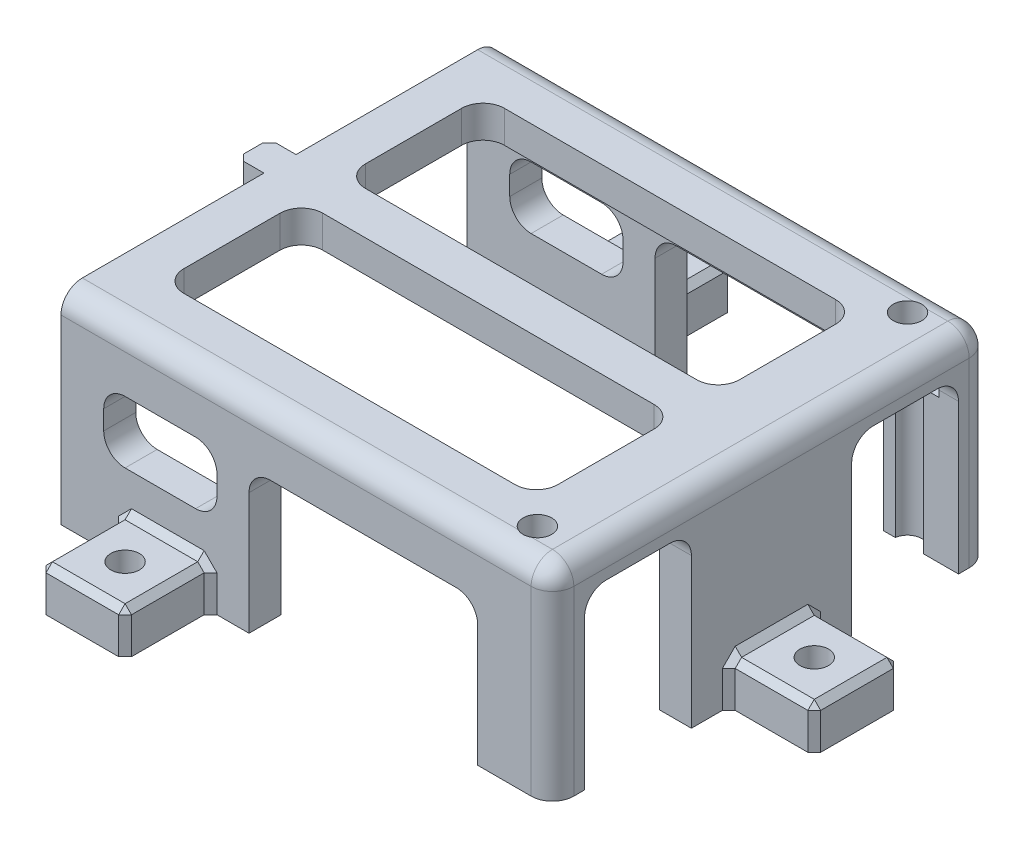
SolidWorks part; units mm, degrees
ref_plane "Front Plane" through (0, 0, 0) normal (0, 0, 1) x (1, 0, 0)
ref_plane "Top Plane" through (0, 0, 0) normal (0, 1, 0) x (1, 0, 0)
ref_plane "Right Plane" through (0, 0, 0) normal (1, 0, 0) x (0, 0, -1)
sketch "Sketch1" plane through (0, 0, 0) normal (0, 1, 0) x (1, 0, 0)
  line L0 (-27.305, 22.225) -> (-27.305, 26.035)
  line L1 (-27.305, -22.225) -> (27.305, -22.225)
  line L3 (-27.305, 22.225) -> (27.305, 22.225)
  line L4 (27.305, -22.225) -> (27.305, 22.225)
  line L5 (-27.305, -22.225) -> (27.305, 22.225) construction
  line L6 (-27.305, 22.225) -> (27.305, -22.225) construction
  line L7 (-27.305, -26.035) -> (31.115, -26.035)
  line L9 (-27.305, 26.035) -> (31.115, 26.035)
  line L10 (31.115, -26.035) -> (31.115, 26.035)
  line L11 (-27.305, -22.847) -> (31.115, 26.035) construction
  line L12 (-27.305, 22.847) -> (31.115, -26.035) construction
  line L13 (-27.305, -22.225) -> (-27.305, -26.035)
  point P0 (0, 0)
  point P6 (0, 0)
  dimension "D1" = 54.61
  dimension "D2" = 58.42
  dimension "D3" = 52.07
  dimension "D4" = 44.45
extrude "Boss-Extrude1" add sketch "Sketch1" along normal blind 20.32
sketch "Sketch2" plane through (0, 20.32, 0) normal (0, 1, 0) x (1, 0, 0)
  line L1 (-27.305, 26.035) -> (31.115, 26.035)
  line L2 (-27.305, 26.035) -> (-27.305, -26.035)
  line L3 (-27.305, -26.035) -> (31.115, -26.035)
  line L4 (31.115, 26.035) -> (31.115, -26.035)
extrude "Boss-Extrude2" add sketch "Sketch2" along normal blind 3.81
sketch "Sketch3" plane through (27.305, 0, 0) normal (-1, 0, 0) x (0, 0, 1)
  line L0 (-22.225, 0) -> (22.225, 0) construction
  line L1 (-22.225, 20.32) -> (-9.525, 20.32)
  line L2 (-22.225, 20.32) -> (-22.225, 0)
  line L3 (-22.225, 0) -> (-9.525, 0)
  line L4 (-9.525, 20.32) -> (-9.525, 0)
  line L6 (22.225, 20.32) -> (9.525, 20.32)
  line L7 (22.225, 20.32) -> (22.225, 0)
  line L8 (22.225, 0) -> (9.525, 0)
  line L9 (9.525, 20.32) -> (9.525, 0)
  dimension "D1" = 12.7
extrude "Cut-Extrude1" cut sketch "Sketch3" against normal up to surface (3.81 mm away) up to face at (31.115, 12.065, 0)
fillet "Fillet2" radius 2.54 3 edges at (31.115, 12.065, -26.035) (31.115, 12.065, 26.035) (31.115, 24.13, 0)
sketch "Sketch4" plane through (31.115, 0, 0) normal (1, 0, 0) x (0, 0, -1)
  line L5 (-9.525, 0) -> (9.525, 0) construction
  line L6 (-5.08, 0) -> (5.08, 0)
  line L7 (-5.08, 0) -> (-5.08, 5.08)
  line L8 (-5.08, 5.08) -> (5.08, 5.08)
  line L9 (5.08, 0) -> (5.08, 5.08)
  line L11 (-9.525, 0) -> (-9.525, 20.32) construction
  point P7 (0, 5.08)
  dimension "D1" = 10.16
  dimension "D2" = 5.08
  dimension "D3" = 9.525
extrude "Boss-Extrude3" add sketch "Sketch4" along normal blind 10.16
chamfer "Chamfer1" distance 0.762 angle 45 8 edges at (31.115, 2.54, -5.08) (31.115, 2.54, 5.08) (36.195, 5.08, -5.08) (41.275, 5.08, 0) (36.195, 5.08, 5.08) (31.115, 5.08, 0) (41.275, 2.54, -5.08) (41.275, 2.54, 5.08)
sketch "Sketch5" plane through (0, 0, 26.035) normal (0, 0, 1) x (1, 0, 0)
  line L0 (-27.305, 0) -> (28.575, 0) construction
  line L1 (-19.685, 0) -> (-9.525, 0)
  line L2 (-19.685, 0) -> (-19.685, 5.08)
  line L3 (-19.685, 5.08) -> (-9.525, 5.08)
  line L4 (-9.525, 0) -> (-9.525, 5.08)
  line L5 (-27.305, 24.13) -> (-27.305, 0) construction
  dimension "D1" = 10.16
  dimension "D2" = 5.08
  dimension "D3" = 7.62
extrude "Boss-Extrude4" add sketch "Sketch5" along normal blind 10.16
chamfer "Chamfer2" distance 0.762 angle 45 8 edges at (-9.525, 2.54, 26.035) (-19.685, 2.54, 26.035) (-9.525, 5.08, 31.115) (-9.525, 2.54, 36.195) (-14.605, 5.08, 36.195) (-14.605, 5.08, 26.035) (-19.685, 5.08, 31.115) (-19.685, 2.54, 36.195)
mirror "Mirror1" about plane through (0, 0, 0) normal (0, 0, 1) of "Chamfer2", "Boss-Extrude4"
hole_wizard "M3 Clearance Hole1" positions "Sketch8" profile "Sketch10" hole size "M3" standard "ANSI Metric" end condition up to next
sketch "Sketch8" plane through (0, 5.08, 0) normal (0, 1, 0) x (1, 0, 0)
  line L0 (-19.685, -35.433) -> (-19.685, -26.797) construction
  line L1 (-10.287, -36.195) -> (-18.923, -36.195) construction
  point P0 (-14.605, -31.115)
  dimension "D1" = 5.08
  dimension "D2" = 5.08
sketch "Sketch10" plane through (-14.605, 5.08, 31.115) normal (1, 0, 0) x (0, 0, 1)
  line L0 (0, 0) -> (0, 5.081)
  line L1 (0, 5.081) -> (1.7, 5.081)
  line L2 (1.7, 5.081) -> (1.7, 0)
  line L5 (1.7, 0) -> (0, 0)
  line L11 (0, -6.35) -> (0, 107.95) construction
  dimension "Thru Hole Dia." = 3.4
  dimension "Thru Hole Depth" = 5.081
mirror "Mirror2" about plane through (0, 0, 0) normal (0, 0, 1) of "M3 Clearance Hole1"
hole_wizard "M3 Clearance Hole2" positions "Sketch11" profile "Sketch12" hole size "M3" standard "ANSI Metric" end condition up to next
sketch "Sketch11" plane through (0, 5.08, 0) normal (0, 1, 0) x (1, 0, 0)
  line L0 (41.275, 4.318) -> (41.275, -4.318) construction
  point P0 (36.195, 0)
  dimension "D1" = 5.08
sketch "Sketch12" plane through (36.195, 5.08, 0) normal (1, 0, 0) x (0, 0, 1)
  line L0 (0, 0) -> (0, 5.08)
  line L1 (0, 5.08) -> (1.7, 5.08)
  line L2 (1.7, 5.08) -> (1.7, 0)
  line L5 (1.7, 0) -> (0, 0)
  line L11 (0, -6.35) -> (0, 107.95) construction
  dimension "Thru Hole Dia." = 3.4
  dimension "Thru Hole Depth" = 5.08
sketch "Sketch13" plane through (0, 24.13, 0) normal (0, 1, 0) x (1, 0, 0)
  line L0 (22.225, -2.54) -> (22.225, -19.05)
  line L1 (22.225, 19.05) -> (-22.225, 19.05)
  line L2 (22.225, 19.05) -> (22.225, 2.54)
  line L3 (22.225, -19.05) -> (-22.225, -19.05)
  line L4 (-22.225, 19.05) -> (-22.225, 2.54)
  line L5 (22.225, 19.05) -> (-22.225, -19.05) construction
  line L6 (22.225, -19.05) -> (-22.225, 19.05) construction
  line L7 (22.225, 2.54) -> (-22.225, 2.54)
  line L9 (22.225, -2.54) -> (-22.225, -2.54)
  line L11 (22.225, 2.54) -> (-22.225, -2.54) construction
  line L12 (22.225, -2.54) -> (-22.225, 2.54) construction
  line L13 (-22.225, -2.54) -> (-22.225, -19.05)
  point P0 (0, 0)
  point P6 (0, 0)
  dimension "D1" = 44.45
  dimension "D2" = 38.1
  dimension "D3" = 5.08
extrude "Cut-Extrude2" cut sketch "Sketch13" against normal up to next
sketch "Sketch14" plane through (0, 0, -26.035) normal (0, 0, -1) x (-1, 0, 0)
  line L0 (-28.575, 0) -> (8.763, 0) construction
  line L1 (-24.123, 0) -> (5.087, 0)
  line L2 (-24.123, 0) -> (-24.123, 19.05)
  line L3 (-24.123, 19.05) -> (4.1472, 19.05)
  line L4 (5.087, 0) -> (5.087, 7.62)
  line L6 (4.1472, 19.05) -> (20.327, 19.05)
  line L8 (5.087, 7.62) -> (20.327, 7.62)
  line L9 (20.327, 19.05) -> (20.327, 7.62)
  point P9 (-24.123, 9.525)
  dimension "D1" = 44.45
  dimension "D2" = 19.05
  dimension "D3" = 11.43
  dimension "D4" = 15.24
sketch "Sketch15" plane through (0, 0, -26.035) normal (0, 0, -1) x (-1, 0, 0)
  line L0 (-28.575, 0) -> (8.763, 0) construction
  line L1 (-22.225, 0) -> (4.953, 0)
  line L2 (-22.225, 0) -> (-22.225, 17.018)
  line L4 (4.953, 0) -> (4.953, 9.652)
  line L5 (-28.575, 24.13) -> (-28.575, 0) construction
  line L8 (8.763, 9.652) -> (22.225, 9.652)
  line L9 (22.225, 17.018) -> (22.225, 9.652)
  line L11 (8.763, 0) -> (8.763, 4.318) construction
  line L12 (10.287, 5.842) -> (18.923, 5.842) construction
  line L13 (8.763, 17.018) -> (22.225, 17.018)
  line L15 (4.953, 9.652) -> (4.953, 17.018)
  line L17 (8.763, 9.652) -> (8.763, 17.018)
  line L18 (-22.225, 17.018) -> (4.953, 17.018)
  point P20 (4.953, 13.335)
  dimension "D1" = 6.35
  dimension "D3" = 44.45
  dimension "D4" = 3.81
  dimension "D5" = 3.81
  dimension "D6" = 3.81
extrude "Cut-Extrude4" cut sketch "Sketch15" against normal through all
fillet "Fillet3" radius 2.54 24 edges at (-8.763, 9.652, 24.13) (-8.763, 17.018, 24.13) (-22.225, 9.652, 24.13) (-22.225, 17.018, 24.13) (29.21, 20.32, 9.525) (1.905, 20.32, 22.225) (29.21, 20.32, -9.525) (1.905, 20.32, -22.225) (-8.763, 9.652, -24.13) (-22.225, 9.652, -24.13) (-8.763, 17.018, -24.13) (-22.225, 17.018, -24.13) (22.225, 22.225, -2.54) (-22.225, 22.225, -19.05) (-22.225, 22.225, -2.54) (22.225, 22.225, -19.05) (22.225, 22.225, 2.54) (-22.225, 22.225, 2.54) (-22.225, 22.225, 19.05) (22.225, 22.225, 19.05) (22.225, 17.018, 24.13) (-4.953, 17.018, 24.13) (-4.953, 17.018, -24.13) (22.225, 17.018, -24.13)
sketch "Sketch16" plane through (0, 24.13, 0) normal (0, 1, 0) x (1, 0, 0)
  line L0 (-27.305, 26.035) -> (-27.305, -26.035) construction
  line L1 (-24.13, 1.905) -> (-30.48, 1.905)
  line L2 (-24.13, 1.905) -> (-24.13, -1.905)
  line L3 (-24.13, -1.905) -> (-30.48, -1.905)
  line L4 (-30.48, 1.905) -> (-30.48, -1.905)
  line L5 (-24.13, 1.905) -> (-30.48, -1.905) construction
  line L6 (-24.13, -1.905) -> (-30.48, 1.905) construction
  point P0 (-27.305, 0)
  dimension "D1" = 3.81
  dimension "D2" = 6.35
extrude "Boss-Extrude5" add sketch "Sketch16" against normal up to surface (3.81 mm away) up to face at (0, 20.32, 10.795)
chamfer "Chamfer3" distance 0.762 angle 45 5 edges at (-30.48, 22.225, -1.905) (-30.48, 22.225, 1.905) (-28.8925, 20.32, -1.905) (-30.48, 20.32, 0) (-28.8925, 20.32, 1.905)
hole_wizard "M3 Clearance Hole4" positions "Sketch20" profile "Sketch21" hole size "M3" standard "ANSI Metric" end condition through all
sketch "Sketch20" plane through (0, 24.13, 0) normal (0, 1, 0) x (1, 0, 0)
  line L0 (19.685, -2.54) -> (-19.685, -2.54) construction
  point P0 (25.2869, -21.9964)
  point P2 (25.2869, 21.9964)
  dimension "D1" = 19.4564
  dimension "D2" = 43.9928
sketch "Sketch21" plane through (25.2869, 24.13, 21.9964) normal (1, 0, 0) x (0, 0, 1)
  line L0 (0, 0) -> (0, 24.13)
  line L1 (0, 24.13) -> (1.7, 24.13)
  line L2 (1.7, 24.13) -> (1.7, 0)
  line L5 (1.7, 0) -> (0, 0)
  line L11 (0, -6.35) -> (0, 107.95) construction
  dimension "Thru Hole Dia." = 3.4
  dimension "Thru Hole Depth" = 24.13
sketch "Sketch22" plane through (0, 20.32, 0) normal (0, -1, 0) x (1, 0, 0)
  line L1 (28.953, 21.9964) -> (27.12, 25.1714)
  line L2 (27.12, 25.1714) -> (23.4538, 25.1714)
  line L3 (23.4538, 25.1714) -> (21.6207, 21.9964)
  line L4 (21.6207, 21.9964) -> (23.4538, 18.8214)
  line L5 (23.4538, 18.8214) -> (27.12, 18.8214)
  line L6 (27.12, 18.8214) -> (28.953, 21.9964)
  line L7 (28.953, -21.9964) -> (27.12, -18.8214)
  line L8 (27.12, -18.8214) -> (23.4538, -18.8214)
  line L9 (23.4538, -18.8214) -> (21.6207, -21.9964)
  line L10 (21.6207, -21.9964) -> (23.4538, -25.1714)
  line L11 (23.4538, -25.1714) -> (27.12, -25.1714)
  line L12 (27.12, -25.1714) -> (28.953, -21.9964)
  circle A0 centre (25.2869, 21.9964) radius 3.175 construction
  circle A1 centre (25.2869, -21.9964) radius 3.175 construction
  dimension "D1" = 6.35
  dimension "D2" = 6.35
extrude "Cut-Extrude5" cut sketch "Sketch22" along normal blind 3.302
fillet "Fillet4" radius 2.54 4 edges at (30.3711, 23.3861, -25.2911) (30.3711, 23.3861, 25.2911) (0.635, 24.13, -26.035) (0.635, 24.13, 26.035)
equation "\"variable\"=0.375"
equation "\"D3@Sketch4\"=\"variable\""
